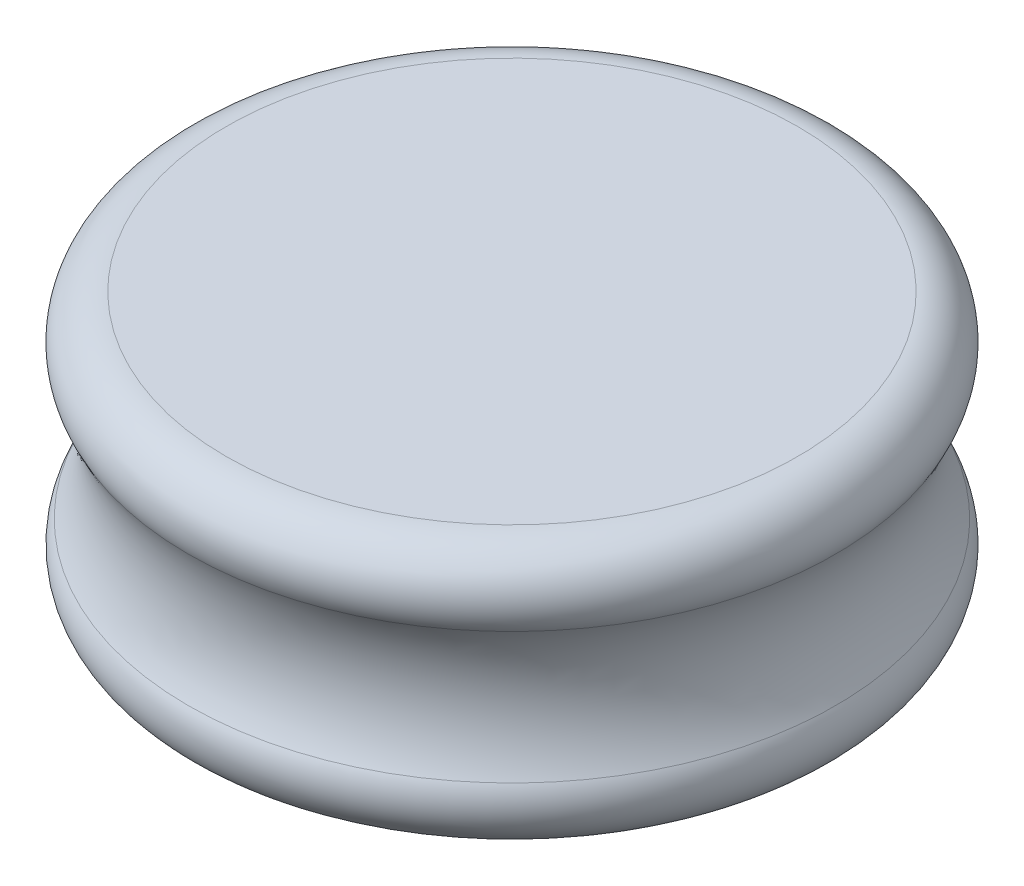
SolidWorks part; units mm, degrees
ref_plane "Front Plane" through (0, 0, 0) normal (0, 0, 1) x (1, 0, 0)
ref_plane "Top Plane" through (0, 0, 0) normal (0, 1, 0) x (1, 0, 0)
ref_plane "Right Plane" through (0, 0, 0) normal (1, 0, 0) x (0, 0, -1)
sketch "Sketch2" plane through (0, 0, 0) normal (0, 0, 1) x (1, 0, 0)
  line L0 (0, 0) -> (0, 12)
  line L1 (0, 0) -> (17, 0)
  line L2 (17, 12) -> (0, 12)
  line L3 (17, 12) -> (17, 11.1962)
  line L4 (17, 0.8038) -> (17, 0)
  arc A0 (17, 11.1962) -> (17, 0.8038) centre (20, 6) ccw
  dimension "D3" = 12
revolve "Revolve1" add sketch "Sketch2" angle 360 about L0
fillet "Fillet4" radius 2 1 edges at (0, 12, -17)
fillet "Fillet5" radius 2 1 edges at (0, 11.1962, -17)
fillet "Fillet6" radius 2 1 edges at (0, 0, -17)
fillet "Fillet7" radius 2 1 edges at (0, 0.8038, -17)
sketch3d "3DSketch4" plane through (0, 0, 0) normal (0, 0, 1) x (1, 0, 0)
  dimension "D1" = 3.5
sketch3d "3DSketch6" plane through (0, 0, 0) normal (0, 0, 1) x (1, 0, 0)
  dimension "D1" = 14
sketch3d "3DSketch7" plane through (0, 0, 0) normal (0, 0, 1) x (1, 0, 0)
